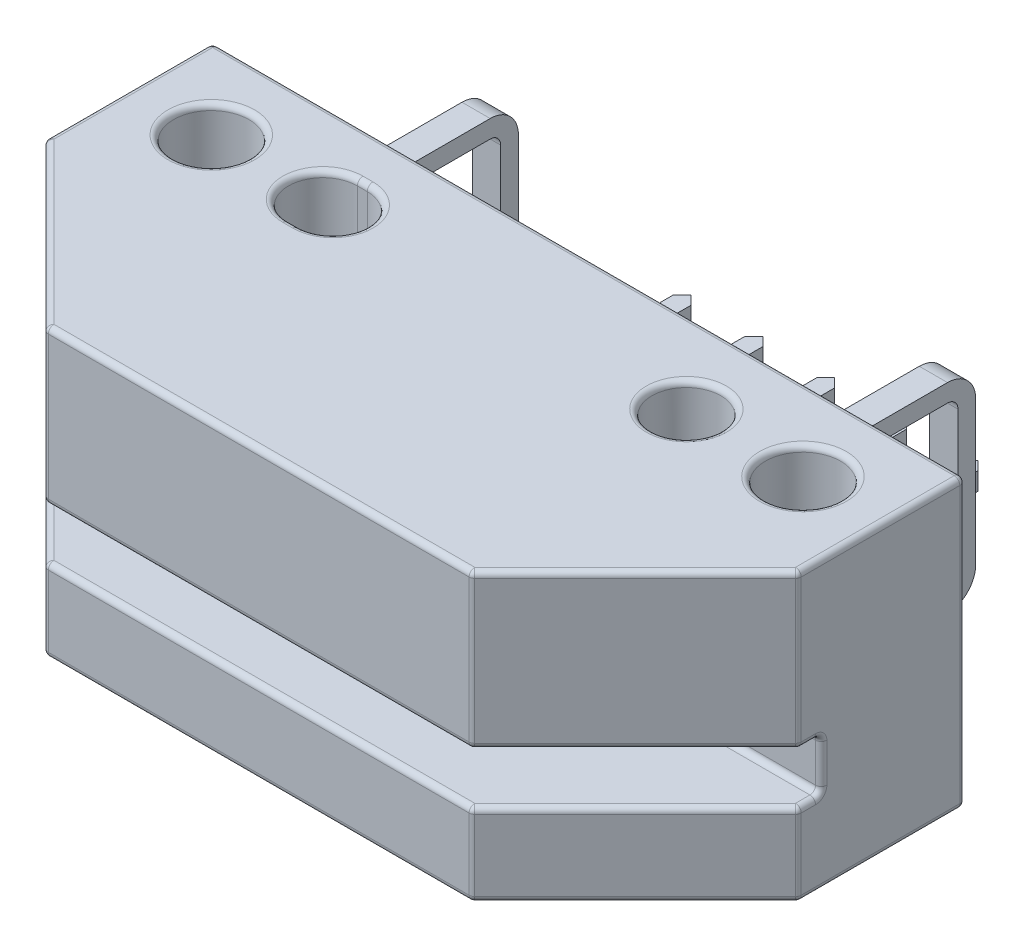
SolidWorks part; units mm, degrees
ref_plane "Front Plane" through (0, 0, 0) normal (0, 0, 1) x (1, 0, 0)
ref_plane "Top Plane" through (0, 0, 0) normal (0, 1, 0) x (1, 0, 0)
ref_plane "Right Plane" through (0, 0, 0) normal (1, 0, 0) x (0, 0, -1)
ref_plane "Gap Center" through (0, 3.81, 0) normal (0, 1, 0) x (1, 0, 0)
ref_plane "Primary Lead Plane" through (0, 1.52, 0) normal (0, 1, 0) x (1, 0, 0)
ref_plane "Secondary Lead Plane" through (0, 8.6, 0) normal (0, 1, 0) x (1, 0, 0)
ref_plane "Power Lead" through (-7.6, 0, 0) normal (1, 0, 0) x (0, 0, -1)
ref_axis "Optical Center" through (0, -0.508, 0) along (0, 1, 0)
sketch "Sketch1" plane through (0, 0, 0) normal (0, 1, 0) x (1, 0, 0)
  line L0 (-13.335, 7.65) -> (13.335, 7.65)
  line L1 (13.335, 7.65) -> (13.335, 1.75)
  line L2 (13.335, 1.75) -> (7.535, -4.05)
  line L3 (7.535, -4.05) -> (-7.535, -4.05)
  line L4 (-7.535, -4.05) -> (-13.335, 1.75)
  line L5 (-13.335, 1.75) -> (-13.335, 7.65)
  line L6 (0, -55) -> (0, 55) construction
  line L7 (-55, 0) -> (55, 0) construction
  point P8 (0, 7.65)
  point P9 (0, -4.05)
  dimension "D1" = 5.8
  dimension "D2" = 45
  dimension "D3" = 26.67
  dimension "D4" = 11.7
  dimension "D5" = 7.65
extrude "Boss-Extrude1" add sketch "Sketch1" along normal blind 10.16
sketch "Sketch2" plane through (0, 3.81, 0) normal (0, 1, 0) x (1, 0, 0)
  line L0 (-7.535, -4.05) -> (7.535, -4.05) construction
  line L1 (-13.335, 2.54) -> (13.335, 2.54)
  line L2 (-13.335, 2.54) -> (-13.335, -4.05)
  line L3 (-13.335, -4.05) -> (13.335, -4.05)
  line L4 (13.335, 2.54) -> (13.335, -4.05)
  line L5 (-13.335, 7.65) -> (-13.335, 1.75) construction
  line L6 (13.335, 1.75) -> (13.335, 7.65) construction
  dimension "D1" = 2.54
extrude "Cut-Extrude1" cut sketch "Sketch2" against normal mid plane 1.78
sketch "Sketch3" plane through (0, 1.52, 0) normal (0, 1, 0) x (1, 0, 0)
  line L0 (-0.65, 7.65) -> (-0.65, 9.115)
  line L1 (-0.65, 9.115) -> (-0.315, 9.45)
  line L2 (-0.315, 9.45) -> (-0.315, 16.035)
  line L3 (-0.315, 16.035) -> (0, 16.35)
  line L4 (0, 16.35) -> (0.315, 16.035)
  line L5 (0.315, 16.035) -> (0.315, 9.45)
  line L6 (0.315, 9.45) -> (0.65, 9.115)
  line L7 (0.65, 9.115) -> (0.65, 7.65)
  line L8 (0.65, 7.65) -> (-0.65, 7.65)
  line L9 (13.335, 7.65) -> (-13.335, 7.65) construction
  line L10 (0, -55) -> (0, 55) construction
  point P13 (0, 7.65)
  dimension "D1" = 0.63
  dimension "D2" = 1.3
  dimension "D3" = 1.8
  dimension "D4" = 6.9
extrude "Boss-Extrude2" add sketch "Sketch3" along normal blind 0.63
pattern_linear "LPattern1" count 3 spacing 2.54 along (1, 0, 0) count 3 spacing 2.54 along (-1, 0, 0) of "Boss-Extrude2"
sketch "Sketch4" plane through (0, 0, 0) normal (0, -1, 0) x (1, 0, 0)
  line L0 (13.335, -7.65) -> (-13.335, -7.65) construction
  line L1 (10.48, -4.75) -> (-10.48, -4.75) construction
  line L2 (0, -55) -> (0, 55) construction
  circle A0 centre (10.48, -4.75) radius 1.335
  circle A1 centre (-10.48, -4.75) radius 1.335
  point P6 (0, -4.75)
  dimension "D2" = 2.67
  dimension "D1" = 2.9
  dimension "D3" = 20.96
extrude "Cut-Extrude2" cut sketch "Sketch4" against normal through all
sketch "Sketch5" plane through (0, 0, 0) normal (0, -1, 0) x (1, 0, 0)
  line L0 (-8.455, -1.22) -> (-8.805, -1.22)
  line L1 (-8.805, 1.22) -> (-8.455, 1.22)
  line L2 (55, 0) -> (-55, 0) construction
  circle A0 centre (8.64, 0) radius 1.22
  arc A1 (-8.805, -1.22) -> (-8.805, 1.22) centre (-8.805, 0) cw
  arc A2 (-8.455, 1.22) -> (-8.455, -1.22) centre (-8.455, 0) cw
  point P8 (-8.63, -1.22)
  point P12 (0, 0)
  dimension "D1" = 2.44
  dimension "D2" = 8.64
  dimension "D3" = 0.35
  dimension "D4" = 17.27
extrude "Cut-Extrude3" cut sketch "Sketch5" against normal blind 2.16
sketch "Sketch6" plane through (0, 0, -7.65) normal (0, 0, -1) x (-1, 0, 0)
  line L0 (55, 1.52) -> (-55, 1.52) construction
  line L1 (7.6, 1.52) -> (8.6, 1.52)
  line L2 (7.6, 1.52) -> (7.6, 2.15)
  line L3 (7.6, 2.15) -> (8.6, 2.15)
  line L4 (8.6, 1.52) -> (8.6, 2.15)
  line L5 (7.6, 55) -> (7.6, -55) construction
  dimension "D1" = 1
  dimension "D2" = 0.63
sketch "Sketch7" plane through (-7.6, 0, 0) normal (1, 0, 0) x (0, 0, -1)
  line L0 (7.65, 1.52) -> (11.75, 1.52)
  line L1 (12.75, 2.52) -> (12.75, 7.6)
  line L2 (11.75, 8.6) -> (7.65, 8.6)
  line L3 (55, 8.6) -> (-55, 8.6) construction
  line L5 (7.65, 10.16) -> (7.65, 0) construction
  arc A0 (11.75, 1.52) -> (12.75, 2.52) centre (11.75, 2.52) ccw
  arc A1 (12.75, 7.6) -> (11.75, 8.6) centre (11.75, 7.6) ccw
  dimension "D2" = 1
  dimension "D1" = 5.1
sweep "Sweep1" add profiles "Sketch6" path "Sketch7"
pattern_linear "LPattern3" count 2 spacing 16.2 along (1, 0, 0) of "Sweep1"
sketch "Sketch8" plane through (0, 10.16, 0) normal (0, 1, 0) x (1, 0, 0)
  line L0 (-6.175, 5.97) -> (-6.525, 5.97)
  line L1 (-6.525, 3.53) -> (-6.175, 3.53)
  line L3 (13.335, 7.65) -> (-13.335, 7.65) construction
  circle A0 centre (6.35, 4.75) radius 1.22
  arc A1 (-6.525, 5.97) -> (-6.525, 3.53) centre (-6.525, 4.75) ccw
  arc A2 (-6.175, 3.53) -> (-6.175, 5.97) centre (-6.175, 4.75) ccw
  point P12 (-6.35, 5.97)
  dimension "D1" = 6.35
  dimension "D2" = 2.44
  dimension "D3" = 2.9
  dimension "D4" = 12.7
  dimension "D5" = 0.35
extrude "Cut-Extrude4" cut sketch "Sketch8" against normal blind 2.16
fillet "Fillet2" radius 0.2 36 edges at (-7.535, 1.46, 4.05) (-10.435, 0, 1.15) (-10.435, 2.92, 1.15) (-13.335, 1.46, -1.75) (-13.335, 0, -4.7) (-13.335, 5.08, -7.65) (-13.335, 10.16, -4.7) (-13.335, 7.43, -1.75) (-13.335, 4.7, -2.145) (-13.335, 3.81, -2.54) (-13.335, 2.92, -2.145) (13.335, 4.7, -2.145) (13.335, 3.81, -2.54) (13.335, 2.92, -2.145) (13.335, 1.46, -1.75) (13.335, 7.43, -1.75) (10.435, 10.16, 1.15) (10.435, 2.92, 1.15) (10.435, 0, 1.15) (10.435, 4.7, 1.15) (7.535, 7.43, 4.05) (7.535, 1.46, 4.05) (0, 2.92, 4.05) (0, 0, 4.05) (0, 4.7, 4.05) (0, 10.16, 4.05) (-7.535, 7.43, 4.05) (-10.435, 10.16, 1.15) (-10.435, 4.7, 1.15) (13.335, 0, -4.7) (13.335, 10.16, -4.7) (13.335, 5.08, -7.65) (0, 10.16, -7.65) (0, 0, -7.65) (0, 2.92, -2.54) (0, 4.7, -2.54)
fillet "Fillet3" radius 0.2 14 edges at (-6.35, 10.16, -3.53) (-7.745, 10.16, -4.75) (-6.35, 10.16, -5.97) (-8.63, 0, 1.22) (-7.235, 0, 0) (-8.63, 0, -1.22) (10.48, 10.16, -6.085) (6.35, 10.16, -3.53) (-4.955, 10.16, -4.75) (-10.48, 10.16, -6.085) (10.48, 0, -6.085) (8.64, 0, -1.22) (-10.025, 0, 0) (-10.48, 0, -6.085)
